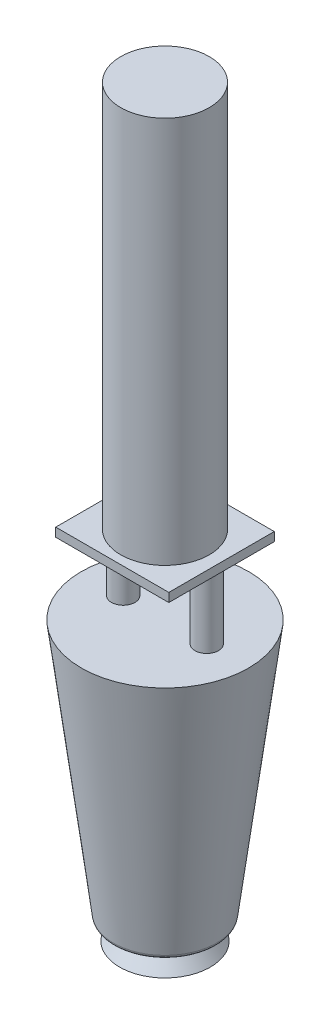
SolidWorks part; units mm, degrees
ref_plane "Front Plane" through (0, 0, 0) normal (0, 0, 1) x (1, 0, 0)
ref_plane "Top Plane" through (0, 0, 0) normal (0, 1, 0) x (1, 0, 0)
ref_plane "Right Plane" through (0, 0, 0) normal (1, 0, 0) x (0, 0, -1)
sketch "Sketch1" plane through (0, 0, 0) normal (0, 0, 1) x (1, 0, 0)
  line L0 (0, 0) -> (0, 63.2)
  line L1 (0, 63.2) -> (19, 63.2)
  line L2 (19, 63.2) -> (11.5884, 4.5553)
  line L3 (11.5884, 4.5553) -> (6.6275, 4.5553)
  line L4 (6.6275, 4.5553) -> (10.3082, 0)
  line L5 (10.3082, 0) -> (0, 0)
  line L6 (0, 0) -> (0, 66.166) construction
  dimension "D1" = 63.2
  dimension "D2" = 19
revolve "Revolve1" add sketch "Sketch1" angle 360 about L6
fillet "Fillet3" radius 1 1 edges at (0, 4.5553, -11.5884)
sketch "Sketch2" plane through (0, 0, 0) normal (0, 0, 1) x (1, 0, 0)
  line L0 (12.1621, 63.2) -> (12.1621, 79)
  line L1 (19, 63.2) -> (-19, 63.2) construction
  line L5 (9.4888, 63.2) -> (9.4888, 84.7068) construction
  line L6 (12.1621, 79) -> (9.4888, 79)
  line L7 (9.4888, 79) -> (9.4888, 63.2)
  line L8 (9.4888, 63.2) -> (12.1621, 63.2)
  dimension "D1" = 15.8
revolve "Revolve2" add sketch "Sketch2" angle 360 about L5
mirror "Mirror1" about plane through (0, 0, 0) normal (1, 0, 0) of "Revolve2"
sketch "Sketch4" plane through (0, 79, 0) normal (0, 1, 0) x (1, 0, 0)
  line L5 (-12.8453, -11.9793) -> (12.8453, -11.9793)
  line L6 (-12.8453, -11.9793) -> (-12.8453, 11.9793)
  line L7 (-12.8453, 11.9793) -> (12.8453, 11.9793)
  line L8 (12.8453, -11.9793) -> (12.8453, 11.9793)
  line L9 (0, 11.9793) -> (0, -11.9793) construction
  line L10 (-12.8453, 0) -> (12.8453, 0) construction
  point P0 (0, 0)
extrude "Boss-Extrude1" add sketch "Sketch4" along normal blind 2
sketch "Sketch5" plane through (0, 0, 0) normal (0, 0, 1) x (1, 0, 0)
  line L0 (0, 81) -> (0, 169)
  line L1 (-12.8453, 81) -> (12.8453, 81) construction
  line L2 (0, 169) -> (10.0571, 169)
  line L3 (10.0571, 169) -> (10.0571, 81)
  line L4 (10.0571, 81) -> (0, 81)
  line L5 (0, 81) -> (0, 182.6656) construction
  dimension "D1" = 88
revolve "Revolve4" add sketch "Sketch5" angle 360 about L5
